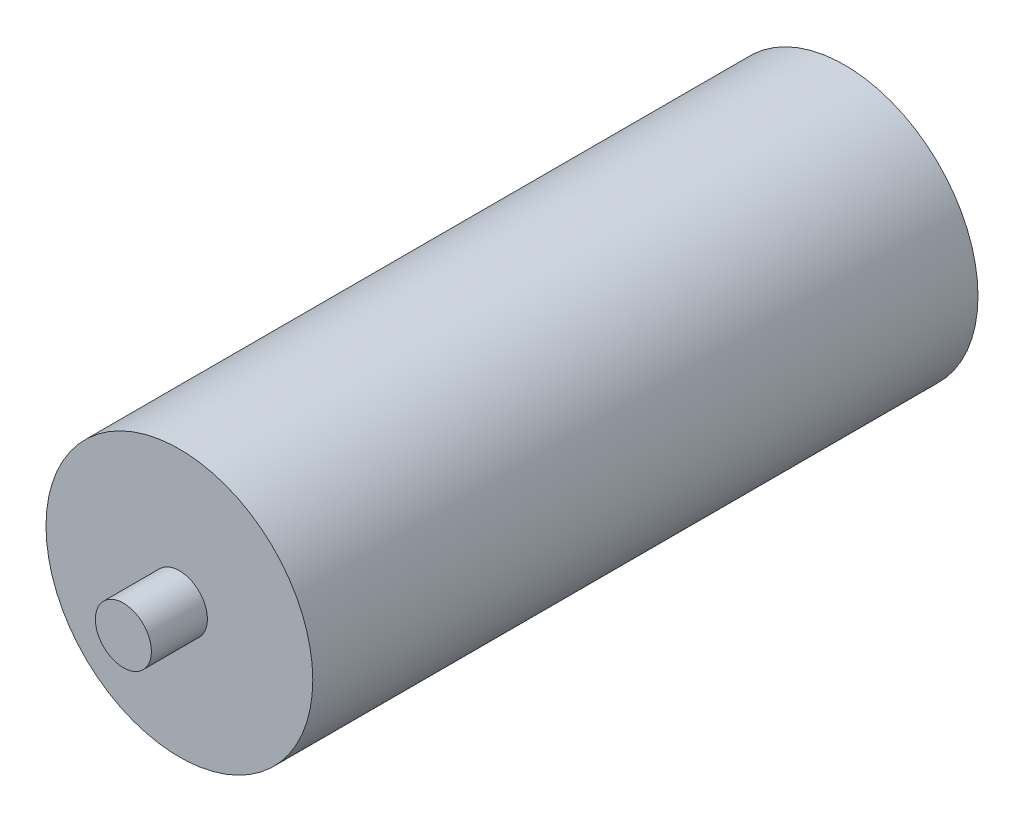
SolidWorks part; units mm, degrees
ref_plane "Front Plane" through (0, 0, 0) normal (0, 0, 1) x (1, 0, 0)
ref_plane "Top Plane" through (0, 0, 0) normal (0, 1, 0) x (1, 0, 0)
ref_plane "Right Plane" through (0, 0, 0) normal (1, 0, 0) x (0, 0, -1)
sketch "Sketch1" plane through (0, 0, 0) normal (0, 0, 1) x (1, 0, 0)
  circle A0 centre (0, 0) radius 19.05
  circle A1 centre (0, 0) radius 4
  dimension "D1" = 38.1
  dimension "D2" = 8
extrude "Boss-Extrude1" add sketch "Sketch1" along normal mid plane 94.996 contours A1 | A0 A1 region at (-18.5112, 0, 0) region at (0, 0, 0)
extrude "Boss-Extrude2" add sketch "Sketch1<3>" along normal mid plane 110.996 contours A1
sketch "Sketch1<3>" plane through (0, 0, 0) normal (0, 0, 1) x (1, 0, 0) same geometry as "Sketch1"
